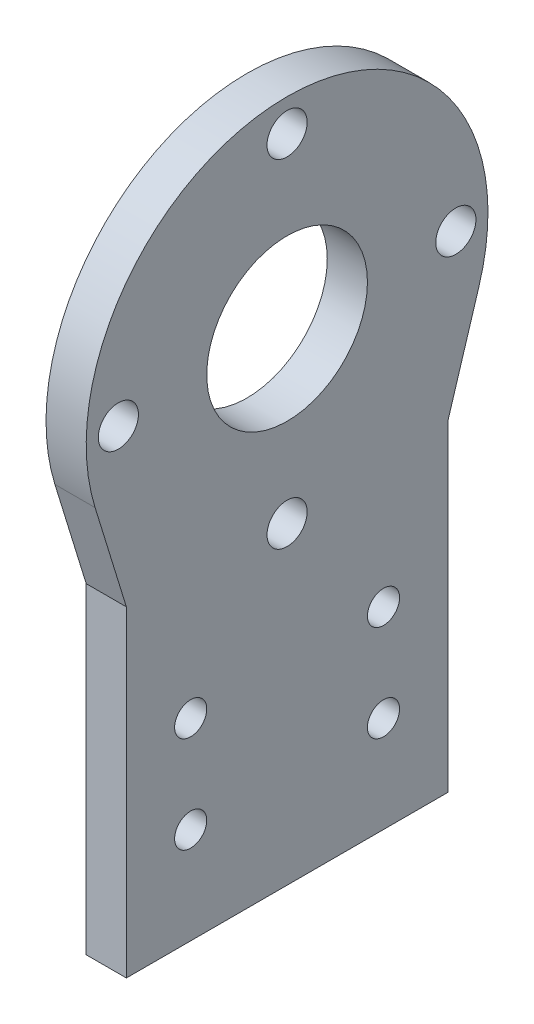
SolidWorks part; units mm, degrees
ref_plane "Alzado" through (0, 0, 0) normal (0, 0, 1) x (1, 0, 0)
ref_plane "Planta" through (0, 0, 0) normal (0, 1, 0) x (1, 0, 0)
ref_plane "Vista lateral" through (0, 0, 0) normal (1, 0, 0) x (0, 0, -1)
sketch "Croquis1" plane through (0, 0, 0) normal (1, 0, 0) x (0, 0, -1)
  line L0 (0, 0) -> (0, 40)
  line L1 (0, 40) -> (40, 40)
  line L2 (40, 40) -> (40, 0)
  line L3 (20, 40) -> (20, 60) construction
  line L4 (0, 0) -> (40, 0)
  line L5 (8, 24) -> (8, 12) construction
  line L6 (0, 40) -> (-3.893, 52.643)
  line L7 (40, 40) -> (43.893, 52.643)
  line L8 (8, 24) -> (32, 24) construction
  line L9 (8, 12) -> (32, 12) construction
  line L10 (32, 12) -> (32, 24) construction
  circle A0 centre (20, 60) radius 25
  circle A1 centre (20, 60) radius 10
  circle A2 centre (8, 24) radius 2
  circle A3 centre (8, 12) radius 2
  circle A4 centre (32, 12) radius 2
  circle A5 centre (32, 24) radius 2
  circle A6 centre (20, 60) radius 21 construction
  circle A7 centre (20, 81) radius 2.5
  circle A8 centre (41, 60) radius 2.5
  circle A9 centre (20, 39) radius 2.5
  circle A10 centre (-1, 60) radius 2.5
  point P31 (20, 60)
  dimension "D2" = 50
  dimension "D4" = 20
  dimension "D7" = 4
  dimension "D12" = 42
  dimension "D13" = 5
  dimension "D1" = 40
  dimension "D3" = 20
  dimension "D5" = 90
  dimension "D6" = 90
  dimension "D8" = 12
  dimension "D9" = 12
  dimension "D10" = 8
  dimension "D11" = 40
  dimension "D14" = 4
extrude "Saliente-Extruir1" add sketch "Croquis1" along normal blind 5 contours A0 L1 A1 | A0 L1 L0 L4 L2 A4 A3 A2 A5 | L1 A0 | A0 L6 L1 | A0 L1 L7 region at (0, 18.8, -20) region at (0, 42.9914, -0.5145) region at (0, 46.0039, -0.102) region at (0, 39.6959, -11.3544) region at (0, 42.9914, -39.4855)
sketch "Croquis2" plane through (5, 0, 0) normal (1, 0, 0) x (0, 0, -1)
  line L5 (40, 0) -> (40, 40)
  line L6 (40, 40) -> (43.893, 52.643)
  line L7 (-3.893, 52.643) -> (0, 40)
  line L8 (0, 40) -> (0, 0)
  line L9 (0, 0) -> (40, 0)
  line L10 (40, 0) -> (40, 40)
  line L11 (40, 40) -> (43.893, 52.643)
  line L12 (-3.893, 52.643) -> (0, 40)
  line L13 (0, 40) -> (0, 0)
  line L14 (0, 0) -> (40, 0)
  circle A0 centre (32, 12) radius 2 construction
  arc A1 (43.893, 52.643) -> (-3.893, 52.643) centre (20, 60) ccw
  arc A2 (43.893, 52.643) -> (-3.893, 52.643) centre (20, 60) ccw
  circle A3 centre (32, 24) radius 2 construction
  circle A4 centre (8, 12) radius 2 construction
  circle A5 centre (8, 24) radius 2 construction
  circle A6 centre (20, 39) radius 2.5 construction
  circle A7 centre (41, 60) radius 2.5 construction
  circle A8 centre (20, 81) radius 2.5 construction
  circle A9 centre (20, 60) radius 10 construction
  circle A10 centre (-1, 60) radius 2.5 construction
  circle A11 centre (32, 12) radius 2
  circle A12 centre (32, 24) radius 2
  circle A13 centre (8, 12) radius 2
  circle A14 centre (8, 24) radius 2
  circle A15 centre (20, 39) radius 2.5
  circle A16 centre (41, 60) radius 2.5
  circle A17 centre (20, 81) radius 2.5
  circle A18 centre (20, 60) radius 10
  circle A19 centre (-1, 60) radius 2.5
  dimension "D1" = 0
